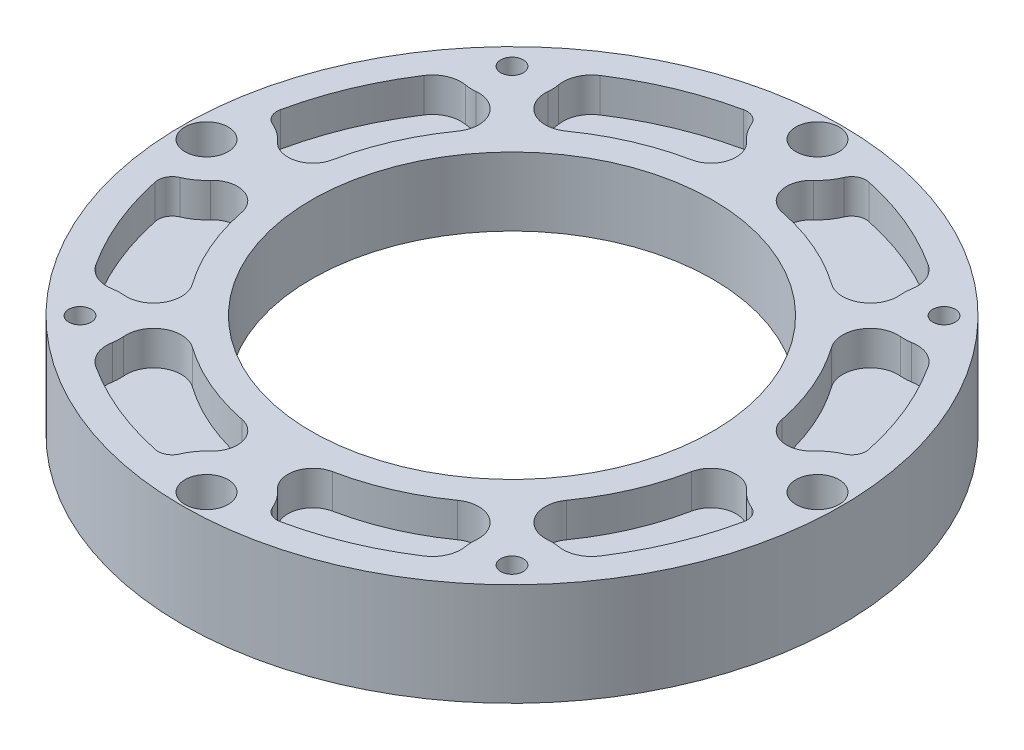
SolidWorks part; units mm, degrees
ref_plane "Front Plane" through (0, 0, 0) normal (0, 0, 1) x (1, 0, 0)
ref_plane "Top Plane" through (0, 0, 0) normal (0, 1, 0) x (1, 0, 0)
ref_plane "Right Plane" through (0, 0, 0) normal (1, 0, 0) x (0, 0, -1)
sketch "Sketch1" plane through (0, 0, 0) normal (0, 1, 0) x (1, 0, 0)
  line L0 (0, 0) -> (42.5, 0) construction
  circle A0 centre (0, 0) radius 45.85
  circle A1 centre (0, 0) radius 27.9
  circle A2 centre (42.5, 0) radius 1.5635
  circle A3 centre (30.052, -30.052) radius 1.5635
  circle A4 centre (0, -42.5) radius 1.5635
  circle A5 centre (0, 0) radius 40.5
  circle A6 centre (-30.052, -30.052) radius 1.5635
  circle A7 centre (-42.5, 0) radius 1.5635
  circle A8 centre (-30.052, 30.052) radius 1.5635
  circle A9 centre (0, 42.5) radius 1.5635
  circle A10 centre (30.052, 30.052) radius 1.5635
  point P13 (0, 0)
  dimension "D1" = 91.7
  dimension "D2" = 55.8
  dimension "D4" = 3.127
  dimension "D6" = 81
  dimension "D3" = 42.5
  dimension "D5" = 8
extrude "Boss-Extrude1" add sketch "Sketch1" against normal blind 4.7625 contours A0 A5 A2 A4 A3 region at (-44.5532, 0, 0)
extrude "Boss-Extrude2" add sketch "Sketch1<4>" along normal blind 4.7625 contours A1 A5 | A0 A5 A2 A4 A3 region at (-44.5532, 0, 0) region at (-39.3545, 0, 0)
sketch "Sketch1<4>" plane through (0, 0, 0) normal (0, 1, 0) x (1, 0, 0) same geometry as "Sketch1"
sketch "Sketch4" plane through (0, 4.7625, 0) normal (0, 1, 0) x (1, 0, 0)
  line L0 (28.4932, -27.352) -> (26.9343, -30.052)
  line L7 (30.052, 33.1697) -> (27.352, 31.6109)
  line L8 (27.352, 31.6109) -> (27.352, 28.4932)
  line L9 (27.352, 28.4932) -> (30.052, 26.9343)
  line L10 (30.052, 26.9343) -> (32.752, 28.4932)
  line L11 (32.752, 28.4932) -> (32.752, 31.6109)
  line L12 (32.752, 31.6109) -> (30.052, 33.1697)
  line L13 (31.6109, -27.352) -> (28.4932, -27.352)
  line L14 (33.1697, -30.052) -> (31.6109, -27.352)
  line L15 (31.6109, -32.752) -> (33.1697, -30.052)
  line L16 (28.4932, -32.752) -> (31.6109, -32.752)
  line L17 (26.9343, -30.052) -> (28.4932, -32.752)
  line L18 (-27.352, -28.4932) -> (-30.052, -26.9343)
  line L19 (-27.352, -31.6109) -> (-27.352, -28.4932)
  line L20 (-30.052, -33.1697) -> (-27.352, -31.6109)
  line L21 (-32.752, -31.6109) -> (-30.052, -33.1697)
  line L22 (-32.752, -28.4932) -> (-32.752, -31.6109)
  line L23 (-30.052, -26.9343) -> (-32.752, -28.4932)
  line L24 (-28.4932, 27.352) -> (-26.9343, 30.052)
  line L25 (-31.6109, 27.352) -> (-28.4932, 27.352)
  line L26 (-33.1697, 30.052) -> (-31.6109, 27.352)
  line L27 (-31.6109, 32.752) -> (-33.1697, 30.052)
  line L28 (-28.4932, 32.752) -> (-31.6109, 32.752)
  line L29 (-26.9343, 30.052) -> (-28.4932, 32.752)
  circle A0 centre (30.052, 30.052) radius 2.7 construction
  point P1 (31.402, 32.3903)
  point P32 (0, 0)
  dimension "D1" = 5.4
  dimension "D2" = 4
extrude "Cut-Extrude2" cut sketch "Sketch4" against normal blind 4.7625
sketch "Sketch3" plane through (0, 4.7625, 0) normal (0, 1, 0) x (1, 0, 0)
  circle A6 centre (0, -42.5) radius 1.5635 construction
  circle A7 centre (42.5, 0) radius 1.5635 construction
  circle A8 centre (0, 42.5) radius 1.5635 construction
  circle A9 centre (-42.5, 0) radius 1.5635 construction
  circle A10 centre (0, 0) radius 27.9 construction
  circle A11 centre (0, 0) radius 45.85 construction
  circle A12 centre (0, -42.5) radius 1.5635
  circle A13 centre (42.5, 0) radius 1.5635
  circle A14 centre (0, 42.5) radius 1.5635
  circle A15 centre (-42.5, 0) radius 1.5635
  circle A16 centre (0, 0) radius 27.9
  circle A17 centre (0, 0) radius 45.85
  circle A18 centre (0, 42.5) radius 3
  circle A19 centre (42.5, 0) radius 3
  circle A20 centre (0, -42.5) radius 3
  circle A21 centre (-42.5, 0) radius 3
  circle A22 centre (-30.052, 30.052) radius 1.565
  circle A23 centre (30.052, 30.052) radius 1.565
  circle A24 centre (30.052, -30.052) radius 1.565
  circle A25 centre (-30.052, -30.052) radius 1.565
  circle M1 centre (0, 0) radius 27.9
  circle M6 centre (0, 0) radius 45.85
  line M21 (-33.1697, 30.052) -> (-31.6109, 32.752)
  line M22 (-31.6109, 32.752) -> (-28.4932, 32.752)
  line M23 (-28.4932, 32.752) -> (-26.9343, 30.052)
  line M24 (-26.9343, 30.052) -> (-28.4932, 27.352)
  line M25 (-28.4932, 27.352) -> (-31.6109, 27.352)
  line M26 (-31.6109, 27.352) -> (-33.1697, 30.052)
  line M27 (-30.052, -33.1697) -> (-32.752, -31.6109)
  line M28 (-32.752, -31.6109) -> (-32.752, -28.4932)
  line M29 (-32.752, -28.4932) -> (-30.052, -26.9343)
  line M30 (-30.052, -26.9343) -> (-27.352, -28.4932)
  line M31 (-27.352, -28.4932) -> (-27.352, -31.6109)
  line M32 (-27.352, -31.6109) -> (-30.052, -33.1697)
  line M33 (33.1697, -30.052) -> (31.6109, -32.752)
  line M34 (31.6109, -32.752) -> (28.4932, -32.752)
  line M35 (28.4932, -32.752) -> (26.9343, -30.052)
  line M36 (26.9343, -30.052) -> (28.4932, -27.352)
  line M37 (28.4932, -27.352) -> (31.6109, -27.352)
  line M38 (31.6109, -27.352) -> (33.1697, -30.052)
  line M39 (30.052, 33.1697) -> (32.752, 31.6109)
  line M40 (32.752, 31.6109) -> (32.752, 28.4932)
  line M41 (32.752, 28.4932) -> (30.052, 26.9343)
  line M42 (30.052, 26.9343) -> (27.352, 28.4932)
  line M43 (27.352, 28.4932) -> (27.352, 31.6109)
  line M44 (27.352, 31.6109) -> (30.052, 33.1697)
  dimension "D1" = 6
  dimension "D2" = 3.13
extrude "Boss-Extrude3" add sketch "Sketch3" along normal blind 4.7625 contours A21 A20 A19 A18 M6 M1 M44 M39 M40 M41 M42 M43 M38 M33 M34 M35 M36 M37 M32 M27 M28 M29 M30 M31 M26 M21 M22 M23 M24 M25 | A22 M21 M26 M25 M24 M23 M22 | A23 M39 M44 M43 M42 M41 M40 | A24 M33 M38 M37 M36 M35 M34 | A25 M27 M32 M31 M30 M29 M28 region at (-45.7203, 4.7625, 0) region at (-32.3189, 4.7625, -31.3608) region at (-31.3608, 4.7625, 32.3189) region at (32.3189, 4.7625, 31.3608) region at (31.3608, 4.7625, -32.3189)
sketch "Sketch5" plane through (0, 9.525, 0) normal (0, 1, 0) x (1, 0, 0)
  line L0 (0, 0) -> (30.052, 30.052) construction
  circle A0 centre (0, 42.5) radius 3 construction
  circle A1 centre (30.052, 30.052) radius 1.565 construction
  circle A2 centre (42.5, 0) radius 3 construction
  circle A3 centre (30.052, -30.052) radius 1.565 construction
  circle A4 centre (0, -42.5) radius 3 construction
  circle A5 centre (-30.052, -30.052) radius 1.565 construction
  circle A6 centre (-42.5, 0) radius 3 construction
  circle A7 centre (-30.052, 30.052) radius 1.565 construction
  circle A8 centre (0, 0) radius 45.85 construction
  circle A9 centre (0, 0) radius 27.9 construction
  circle A10 centre (0, 42.5) radius 3
  circle A11 centre (30.052, 30.052) radius 1.565
  circle A12 centre (42.5, 0) radius 3
  circle A13 centre (30.052, -30.052) radius 1.565
  circle A14 centre (0, -42.5) radius 3
  circle A15 centre (-30.052, -30.052) radius 1.565
  circle A16 centre (-42.5, 0) radius 3
  circle A17 centre (-30.052, 30.052) radius 1.565
  circle A18 centre (0, 0) radius 45.85
  circle A19 centre (0, 0) radius 27.9
  arc A20 (6.31, 31.2697) -> (18.4511, 26.0224) centre (0, 0) cw
  arc A21 (4.6718, 37.2871) -> (6.4423, 39.762) centre (0, 42.5) ccw
  arc A22 (24.5734, 31.0284) -> (24.5119, 29.527) centre (30.052, 30.052) ccw
  arc A23 (24.5119, 29.527) -> (18.4511, 26.0224) centre (20.6784, 29.1636) cw
  arc A24 (4.6718, 37.2871) -> (6.31, 31.2697) centre (7, 34.6892) ccw
  arc A25 (22.8162, 35.0834) -> (24.5734, 31.0284) centre (20.6354, 31.7302) cw
  arc A26 (8.6987, 40.936) -> (6.4423, 39.762) centre (8.283, 38.9797) ccw
  arc A27 (22.8162, 35.0834) -> (8.6987, 40.936) centre (0, 0) ccw
  arc A28 (35.0834, 22.8162) -> (31.0284, 24.5734) centre (31.7302, 20.6354) ccw
  arc A29 (31.0284, 24.5734) -> (29.527, 24.5119) centre (30.052, 30.052) cw
  arc A30 (29.527, 24.5119) -> (26.0224, 18.4511) centre (29.1636, 20.6784) ccw
  arc A31 (31.2697, 6.31) -> (26.0224, 18.4511) centre (0, 0) ccw
  arc A32 (35.0834, 22.8162) -> (40.936, 8.6987) centre (0, 0) cw
  arc A33 (40.936, 8.6987) -> (39.762, 6.4423) centre (38.9797, 8.283) cw
  arc A34 (37.2871, 4.6718) -> (39.762, 6.4423) centre (42.5, 0) cw
  arc A35 (37.2871, 4.6718) -> (31.2697, 6.31) centre (34.6892, 7) cw
  arc A36 (37.2871, -4.6718) -> (31.2697, -6.31) centre (34.6892, -7) ccw
  arc A37 (31.2697, -6.31) -> (26.0224, -18.4511) centre (0, 0) cw
  arc A38 (29.527, -24.5119) -> (26.0224, -18.4511) centre (29.1636, -20.6784) cw
  arc A39 (31.0284, -24.5734) -> (29.527, -24.5119) centre (30.052, -30.052) ccw
  arc A40 (35.0834, -22.8162) -> (31.0284, -24.5734) centre (31.7302, -20.6354) cw
  arc A41 (35.0834, -22.8162) -> (40.936, -8.6987) centre (0, 0) ccw
  arc A42 (40.936, -8.6987) -> (39.762, -6.4423) centre (38.9797, -8.283) ccw
  arc A43 (37.2871, -4.6718) -> (39.762, -6.4423) centre (42.5, 0) ccw
  arc A44 (24.5119, -29.527) -> (18.4511, -26.0224) centre (20.6784, -29.1636) ccw
  arc A45 (24.5734, -31.0284) -> (24.5119, -29.527) centre (30.052, -30.052) cw
  arc A46 (22.8162, -35.0834) -> (24.5734, -31.0284) centre (20.6354, -31.7302) ccw
  arc A47 (22.8162, -35.0834) -> (8.6987, -40.936) centre (0, 0) cw
  arc A48 (6.31, -31.2697) -> (18.4511, -26.0224) centre (0, 0) ccw
  arc A49 (4.6718, -37.2871) -> (6.31, -31.2697) centre (7, -34.6892) cw
  arc A50 (4.6718, -37.2871) -> (6.4423, -39.762) centre (0, -42.5) cw
  arc A51 (8.6987, -40.936) -> (6.4423, -39.762) centre (8.283, -38.9797) cw
  arc A52 (-4.6718, -37.2871) -> (-6.31, -31.2697) centre (-7, -34.6892) ccw
  arc A53 (-6.31, -31.2697) -> (-18.4511, -26.0224) centre (0, 0) cw
  arc A54 (-24.5119, -29.527) -> (-18.4511, -26.0224) centre (-20.6784, -29.1636) cw
  arc A55 (-24.5734, -31.0284) -> (-24.5119, -29.527) centre (-30.052, -30.052) ccw
  arc A56 (-22.8162, -35.0834) -> (-24.5734, -31.0284) centre (-20.6354, -31.7302) cw
  arc A57 (-22.8162, -35.0834) -> (-8.6987, -40.936) centre (0, 0) ccw
  arc A58 (-8.6987, -40.936) -> (-6.4423, -39.762) centre (-8.283, -38.9797) ccw
  arc A59 (-4.6718, -37.2871) -> (-6.4423, -39.762) centre (0, -42.5) ccw
  arc A60 (-29.527, -24.5119) -> (-26.0224, -18.4511) centre (-29.1636, -20.6784) ccw
  arc A61 (-31.0284, -24.5734) -> (-29.527, -24.5119) centre (-30.052, -30.052) cw
  arc A62 (-35.0834, -22.8162) -> (-31.0284, -24.5734) centre (-31.7302, -20.6354) ccw
  arc A63 (-35.0834, -22.8162) -> (-40.936, -8.6987) centre (0, 0) cw
  arc A64 (-31.2697, -6.31) -> (-26.0224, -18.4511) centre (0, 0) ccw
  arc A65 (-37.2871, -4.6718) -> (-31.2697, -6.31) centre (-34.6892, -7) cw
  arc A66 (-37.2871, -4.6718) -> (-39.762, -6.4423) centre (-42.5, 0) cw
  arc A67 (-40.936, -8.6987) -> (-39.762, -6.4423) centre (-38.9797, -8.283) cw
  arc A68 (-37.2871, 4.6718) -> (-31.2697, 6.31) centre (-34.6892, 7) ccw
  arc A69 (-31.2697, 6.31) -> (-26.0224, 18.4511) centre (0, 0) cw
  arc A70 (-29.527, 24.5119) -> (-26.0224, 18.4511) centre (-29.1636, 20.6784) cw
  arc A71 (-31.0284, 24.5734) -> (-29.527, 24.5119) centre (-30.052, 30.052) ccw
  arc A72 (-35.0834, 22.8162) -> (-31.0284, 24.5734) centre (-31.7302, 20.6354) cw
  arc A73 (-35.0834, 22.8162) -> (-40.936, 8.6987) centre (0, 0) ccw
  arc A74 (-40.936, 8.6987) -> (-39.762, 6.4423) centre (-38.9797, 8.283) ccw
  arc A75 (-37.2871, 4.6718) -> (-39.762, 6.4423) centre (-42.5, 0) ccw
  arc A76 (-24.5119, 29.527) -> (-18.4511, 26.0224) centre (-20.6784, 29.1636) ccw
  arc A77 (-24.5734, 31.0284) -> (-24.5119, 29.527) centre (-30.052, 30.052) cw
  arc A78 (-22.8162, 35.0834) -> (-24.5734, 31.0284) centre (-20.6354, 31.7302) ccw
  arc A79 (-22.8162, 35.0834) -> (-8.6987, 40.936) centre (0, 0) cw
  arc A80 (-6.31, 31.2697) -> (-18.4511, 26.0224) centre (0, 0) ccw
  arc A81 (-4.6718, 37.2871) -> (-6.31, 31.2697) centre (-7, 34.6892) cw
  arc A82 (-4.6718, 37.2871) -> (-6.4423, 39.762) centre (0, 42.5) cw
  arc A83 (-8.6987, 40.936) -> (-6.4423, 39.762) centre (-8.283, 38.9797) cw
  point P137 (0, 0)
  dimension "D1" = 4
  dimension "D2" = 4
  dimension "D3" = 4
  dimension "D4" = 4
  dimension "D5" = 12
  dimension "D8" = 2
  dimension "D9" = 4
  dimension "D7" = 14
  dimension "D6" = 4
extrude "Cut-Extrude3" cut sketch "Sketch5" against normal blind 4.7625 contours A75 A68 A69 A70 A71 A72 A73 A74 | A83 A79 A78 A77 A76 A80 A81 A82 | A25 A27 A26 A21 A24 A20 A23 A22 | A35 A34 A33 A32 A28 A29 A30 A31 | A43 A36 A37 A38 A39 A40 A41 A42 | A51 A47 A46 A45 A44 A48 A49 A50 | A59 A52 A53 A54 A55 A56 A57 A58 | A67 A63 A62 A61 A60 A64 A65 A66 region at (14.5651, 9.525, -33.3777) region at (33.3777, 9.525, -14.5651) region at (33.3777, 9.525, 14.5651) region at (14.5651, 9.525, 33.3777) region at (-14.5651, 9.525, 33.3777) region at (-33.3777, 9.525, 14.5651) region at (-33.3777, 9.525, -14.5651) region at (-14.5651, 9.525, -33.3777)
equation "\"bearing_21_OD\"= 21mm"
equation "\"pin_cirlce_diameter\"= 75mm"
equation "\"pin_diam\"= 6mm"
equation "\"gear_thickness\"= 4mm"
equation "\"ball_bearing_diam\"= 3.214mm"
equation "\"bearing_21_outer_clearance\"= 0.127mm'change this"
equation "\"bearing_15_OD\"= 15mm"
equation "\"bearing_15_outer_clearance\"= 0mm'change this"
equation "\"thrust_bearing_thickness\"= 5mm'measure this irl and change"
equation "\"D1@Boss-Extrude1\"=\"sheetThickness\""
equation "\"largeBearOD\"= 21mm"
equation "\"largeBearID\"= 15mm"
equation "\"largeBearOTight\"= 0.34375mm'calibrate - hold onto gears"
equation "\"largeBearITight\"= 0mm'calibrate - hold onto eccentric nut"
equation "\"largeBearFlangeDiam\"= 22.5mm"
equation "\"largeBearFlangeWidth\"= 0.8mm"
equation "\"smallBearOD\"= 14.8mm"
equation "\"smallBearOTight\"= 0mm'calibrate - hold onto bottom of gearbox"
equation "\"smallBearOLoose\"= 0mm'calibrate - able to take off topHat"
equation "\"smallBearID\"= 10mm"
equation "\"smallBearITight\"= 0mm'hold onto "
equation "\"pinCircleDiam\"= 75mm"
equation "\"pinDiam\"= 6mm"
equation "\"sheetThickness\"= 0.1875in"
equation "\"ballBearDiam\"= 3.5mm"
equation "\"thrustBearingThickness\"= 5mm'measure this irl and change"
equation "\"thrustBearingID\"= 0mm'measure this irl and change"
equation "\"thrustBearingOD\"= 0mm'measure this irl and change"
equation "\"eccentricity\"= 1mm"
equation "\"D1@Boss-Extrude2\"=\"sheetThickness\""
equation "\"D1@Boss-Extrude3\"=\"sheetThickness\""
equation "\"D1@Cut-Extrude2\"=\"sheetThickness\""
equation "\"D1@Cut-Extrude3\"=\"sheetThickness\""
